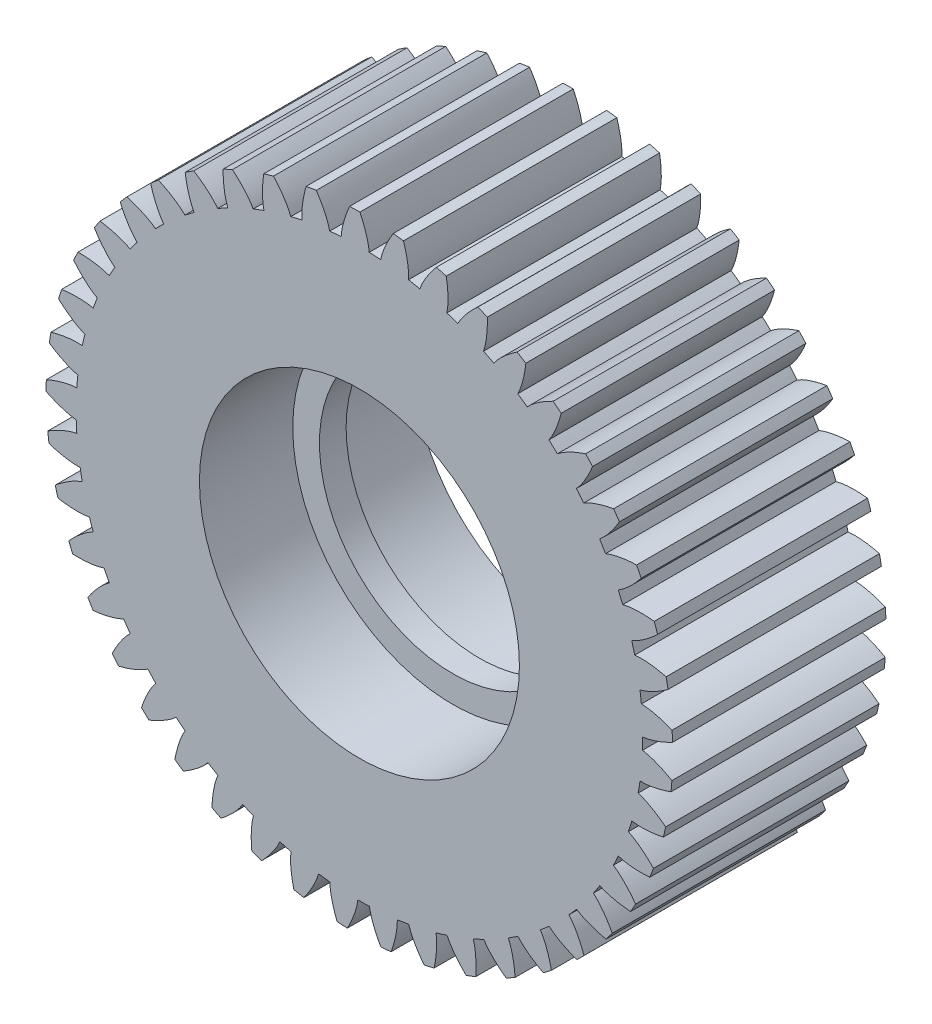
SolidWorks part; units mm, degrees
material "ABS"
ref_plane "Front Plane" through (0, 0, 0) normal (0, 0, 1) x (1, 0, 0)
ref_plane "Top Plane" through (0, 0, 0) normal (0, 1, 0) x (1, 0, 0)
ref_plane "Right Plane" through (0, 0, 0) normal (1, 0, 0) x (0, 0, -1)
sketch "Sketch1" plane through (0, 0, 0) normal (0, 0, 1) x (1, 0, 0)
  circle A0 centre (0, 0) radius 11.75
  dimension "D1" = 23.5
extrude "Boss-Extrude1" add sketch "Sketch1" along normal mid plane 8
sketch "Sketch2" plane through (0, 0, 0) normal (0, 0, 1) x (1, 0, 0)
  line L0 (0, 0) -> (10.5715, 0) construction
  line L1 (0, 0) -> (11.2477, -0.225) construction
  line L2 (0, 0) -> (10.5631, -0.4228) construction
  line L3 (10.5715, 0) -> (10.625, 0)
  line L4 (10.5631, -0.4228) -> (10.6165, -0.4249)
  circle A0 centre (0, 0) radius 11.25 construction
  circle A1 centre (0, 0) radius 10.5715 construction
  circle A2 centre (0, 0) radius 10.625
  circle A3 centre (0, 0) radius 11.75 construction
  circle A4 centre (0, 0) radius 11.75
  spline S0 degree 4 poles (10.5715, 0) (10.5752, 0.0001) (10.5853, 0.0004) (10.6044, 0.0016) (10.6356, 0.0045) (10.6753, 0.0095) (10.7265, 0.0174) (10.7865, 0.0288) (10.8523, 0.0433) (10.9236, 0.0613) (10.9945, 0.0812) (11.0648, 0.1028) (11.1346, 0.126) (11.2188, 0.1559) (11.3192, 0.1944) (11.4357, 0.2433) (11.5668, 0.3032) (11.6991, 0.369) (11.8282, 0.4376) (11.9573, 0.5114) (12.0813, 0.5859) (12.2085, 0.6678) (12.3252, 0.7457) (12.4542, 0.8378) (12.5578, 0.9136) (12.6924, 1.0187) (12.7713, 1.0823) (12.8629, 1.1585) (12.9032, 1.1933) (12.9281, 1.2147) knots 0 0 0 0 0 0.005377 0.015084 0.028532 0.04661 0.064855 0.092111 0.119476 0.146842 0.174209 0.201575 0.228941 0.256307 0.307035 0.361767 0.4165 0.471232 0.525964 0.580697 0.635429 0.690161 0.744894 0.799626 0.854358 0.909091 0.954545 1 1 1 1 1 construction
  spline S1 degree 4 poles (10.5715, 0) (10.5752, 0.0001) (10.5853, 0.0004) (10.6044, 0.0016) (10.6356, 0.0045) (10.6753, 0.0095) (10.7265, 0.0174) (10.7865, 0.0288) (10.8523, 0.0433) (10.9236, 0.0613) (10.9945, 0.0812) (11.0648, 0.1028) (11.1346, 0.126) (11.2188, 0.1559) (11.3192, 0.1944) (11.4357, 0.2433) (11.5668, 0.3032) (11.6991, 0.369) (11.8282, 0.4376) (11.9573, 0.5114) (12.0813, 0.5859) (12.2085, 0.6678) (12.3252, 0.7457) (12.4542, 0.8378) (12.5578, 0.9136) (12.6632, 0.9959) (12.7143, 1.0366) (12.7403, 1.0576) knots 0 0 0 0 0 0.005377 0.015084 0.028532 0.04661 0.064855 0.092111 0.119476 0.146842 0.174209 0.201575 0.228941 0.256307 0.307035 0.361767 0.4165 0.471232 0.525964 0.580697 0.635429 0.690161 0.744894 0.799626 0.854358 0.909091 0.909091 0.909091 0.909091 0.909091
  spline S2 degree 4 poles (10.5631, -0.4228) (10.5667, -0.423) (10.5768, -0.4237) (10.5959, -0.4257) (10.6269, -0.4298) (10.6664, -0.4364) (10.7172, -0.4464) (10.7768, -0.4602) (10.8419, -0.4773) (10.9124, -0.4981) (10.9824, -0.5208) (11.0518, -0.5452) (11.1207, -0.5712) (11.2036, -0.6045) (11.3024, -0.647) (11.4168, -0.7005) (11.5454, -0.7655) (11.675, -0.8366) (11.8012, -0.9103) (11.9273, -0.9892) (12.0482, -1.0686) (12.1721, -1.1555) (12.2856, -1.238) (12.4108, -1.3352) (12.5112, -1.4151) (12.6415, -1.5255) (12.7178, -1.5922) (12.8063, -1.672) (12.8452, -1.7084) (12.8691, -1.7308) knots 0 0 0 0 0 0.005377 0.015084 0.028532 0.04661 0.064855 0.092111 0.119476 0.146842 0.174209 0.201575 0.228941 0.256307 0.307035 0.361767 0.4165 0.471232 0.525964 0.580697 0.635429 0.690161 0.744894 0.799626 0.854358 0.909091 0.954545 1 1 1 1 1 construction
  spline S3 degree 4 poles (10.5631, -0.4228) (10.5667, -0.423) (10.5768, -0.4237) (10.5959, -0.4257) (10.6269, -0.4298) (10.6664, -0.4364) (10.7172, -0.4464) (10.7768, -0.4602) (10.8419, -0.4773) (10.9124, -0.4981) (10.9824, -0.5208) (11.0518, -0.5452) (11.1207, -0.5712) (11.2036, -0.6045) (11.3024, -0.647) (11.4168, -0.7005) (11.5454, -0.7655) (11.675, -0.8366) (11.8012, -0.9103) (11.9273, -0.9892) (12.0482, -1.0686) (12.1721, -1.1555) (12.2856, -1.238) (12.4108, -1.3352) (12.5112, -1.4151) (12.6133, -1.5016) (12.6627, -1.5442) (12.6878, -1.5663) knots 0 0 0 0 0 0.005377 0.015084 0.028532 0.04661 0.064855 0.092111 0.119476 0.146842 0.174209 0.201575 0.228941 0.256307 0.307035 0.361767 0.4165 0.471232 0.525964 0.580697 0.635429 0.690161 0.744894 0.799626 0.854358 0.909091 0.909091 0.909091 0.909091 0.909091
  dimension "D1" = 22.5
  dimension "D2" = 21.1431
  dimension "D3" = 21.25
  dimension "D4" = 1.146
  dimension "D5" = 1.146
extrude "Cut-Extrude1" cut sketch "Sketch2" against normal through all both and the other way through all contours A2 S3 A4 S1 region at (11.2841, -0.2257, 0)
pattern_circular "CirPattern2" count 45 over 360 about axis through (0, 0, 4) along (0, 0, -1) of "Cut-Extrude1"
sketch "Sketch3" plane through (0, 0, 4) normal (0, 0, 1) x (1, 0, 0)
  circle A0 centre (0, 0) radius 6
  dimension "D1" = 12
extrude "Cut-Extrude2" cut sketch "Sketch3" against normal blind 3.5
sketch "Sketch4" plane through (0, 0, 0.5) normal (0, 0, 1) x (1, 0, 0)
  circle A0 centre (0, 0) radius 5
  dimension "D1" = 10
extrude "Cut-Extrude3" cut sketch "Sketch4" against normal through all
mirror "Mirror1" about plane through (0, 0, 0) normal (0, 0, 1) of "Cut-Extrude2"
equation "\"Np\" = 45"
equation "\"module\" = 0.5"
equation "\"pressure angle\" = 20.0"
equation "\"h_a\" = 0.5"
equation "\"h_b\" = 0.625"
equation "\"clr_tip_root\" = 0.125"
equation "\"dp_p\" = 22.5"
equation "\"db_p\" = 21.14308396768294"
equation "\"D1@Sketch1\"= \"dp_p\" + 2*\"h_a\" "
equation "\"fw_p\" = 8.0"
equation "\"D1@Boss-Extrude1\"=\"fw_p\""
equation "\"D1@Sketch2\"=\"dp_p\""
equation "\"D2@Sketch2\"= \"db_p\""
equation "\"D3@Sketch2\"=\"dp_p\"- 2*\"h_b\""
equation "\"alpha_p\" = 0.8539582918412307"
equation "\"D4@Sketch2\"= 360 / ( 4 * \"Np\" ) - \"alpha_p\""
equation "\"beta_p\" = 2.2920834163175385"
equation "\"D5@Sketch2\"= 360 / ( 4 * \"Np\" ) - \"alpha_p\""
equation "\"D1@CirPattern2\"=\"Np\""
equation "\"Nr\" = 123"
equation "\"pressure_angle\" = 20.0"
equation "\"h_f\" = 0.625"
equation "\"dp_r\" = 61.5"
equation "\"db_r\" = 57.79109617833337"
equation "\"fw_r\" = 8.0"
equation "\"alpha_r\" = 0.8539582918412414"
equation "\"beta_r\" = 3.171331217828824"
equation "\"bearing_ID\" = 50"
equation "\"bearing_OD\" = 65"
equation "\"bearing_height\" = 7"
equation "\"clearance_planet\" = 1.5"
equation "\"case_dist\" = 6.5"
equation "\"Motor_case_OD_max\" = 96.5"
equation "\"case_mounting_PCD\" = 89.0"
equation "\"bearing mount thickness\" = 8"
equation "\"case_mounting_hole_dia\" = 3"
equation "\"output_mounting_PCD\" = 73"
equation "\"output_mounting_hole_dia\" = 4"
equation "\"clearance_case_mount_holes_shell_thickness\" = 1"
equation "\"motor_case_OD_base\" = 87.0"
equation "\"sec_carrier_thickness\" = 5"
equation "\"sun_coupler_hub_thickness\" = 4"
equation "\"clearance_sun_coupler_sec_carrier\" = 1.5"
equation "\"clearance_motor_and_case\" = 5"
equation "\"motor_OD\" = 72"
equation "\"Motor_case_thickness\" = 2.5"
equation "\"Motor_case_ID\" = 82"
equation "\"case_mounting_hole_shift\" = 1.0"
equation "\"output_mounting_nut_wrench_size\" = 7"
equation "\"output_mounting_nut_thickness\" = 3.2"
equation "\"case_mounting_hole_allen_socket_dia\" = 5.5"
equation "\"output_mounting_nut_depth\" = 3"
equation "\"case_mounting_bolt_depth\" = 4.5"
equation "\"Ns\" = 33"
equation "\"ring_radial_thickness\" = 5"
equation "\"ring_OD\" = 71.5"
equation "\"ring_to_chamfer_clearance\" = 2"
equation "\"Motor_case_OD_base_to_chamfer\" = 5"
equation "\"pattern_offset_from_motor_case_OD_base\" = 3"
equation "\"pattern_bulge_dia\" = 3"
equation "\"pattern_num_bulge\" = 18"
equation "\"pattern_depth\" = 2"
equation "\"motor_height\" = 27"
equation "\"case_mounting_wrench_size\" = 5.5"
equation "\"case_mounting_nut_clearance\" = 2"
equation "\"base_plate_thickness\" = 4"
equation "\"case_mounting_nut_thickness\" = 2.4"
equation "\"case_mounting_surface_height\" = 4"
equation "\"motor_mount_hole_PCD\" = 32"
equation "\"motor_mount_hole_dia\" = 4"
equation "\"motor_mount_hole_num\" = 4"
equation "\"central_hole_offset_from_motor_mount_PCD\" = 5"
equation "\"wire_slot_dist_from_center\" = 30"
equation "\"wire_slot_length\" = 10"
equation "\"wire_slot_radius\" = 2.5"
equation "\"driver_upper_holes_dist_from_center\" = 23"
equation "\"driver_lower_holes_dist_from_center\" = 15"
equation "\"driver_side_holes_dist_from_center\" = 20"
equation "\"driver_mount_holes_dia\" = 2.5"
equation "\"driver_mount_inserts_OD\" = 3.5"
equation "\"driver_mount_thickness\" = 1.5"
equation "\"driver_mount_height\" = 4"
equation "\"air_flow_hole_offset\" = 3"
equation "\"num_planet\" = 3"
equation "\"planet_pin_bolt_dia\" = 5"
equation "\"planet_pin_socket_head_dia\" = 8.5"
equation "\"carrier_PCD\" = 39.0"
equation "\"planet_shaft_dia\" = 8"
equation "\"planet_shaft_step_offset\" = 1"
equation "\"carrier_trapezoidal_support_sun_offset\" = 5"
equation "\"carrier_trapezoidal_support_hole_PCD_offset_bearing_ID\" = 4"
equation "\"carrier_trapezoidal_support_hole_dia\" = 3"
equation "\"carrier_trapezoidal_support_hole_socket_head_dia\" = 5.5"
equation "\"carrier_bearing_step_width\" = 1.5"
equation "\"standard_clearance_1_5mm\" = 1.5"
equation "\"standard_fillet_1_5mm\" = 1.5"
equation "\"sun_shaft_bearing_OD\" = 16"
equation "\"sun_shaft_bearing_width\" = 5"
equation "\"standard_bearing_insertion_chamfer\" = 0.5"
equation "\"carrier_trapezoidal_support_hole_wrench_size\" = 5.5"
equation "\"planet_pin_bolt_wrench_size\" = 8"
equation "\"planet_bearing_OD\" = 12"
equation "\"planet_bearing_width\" = 3.5"
equation "\"planet_bore\" = 10"
equation "\"D1@Cut-Extrude2\"=\"planet_bearing_width\""
equation "\"D1@Sketch3\"=\"planet_bearing_OD\""
equation "\"D1@Sketch4\"=\"planet_bore\""
equation "\"motor_output_hole_PCD\" = 22"
equation "\"motor_output_hole_dia\" = 3"
equation "\"motor_output_hole_num\" = 4"
equation "\"dp_s\" = 16.5"
equation "\"db_s\" = 15.50492824296749"
equation "\"fw_s_calc\" = 1.2595130854287364"
equation "\"alpha_s\" = 0.8539582918412449"
equation "\"beta_s\" = 3.7466288708629643"
equation "\"sun_shaft_bearing_ID\" = 8"
equation "\"sun_hub_dia\" = 31.0"
equation "\"sun_central_bolt_dia\" = 5"
equation "\"sun_central_bolt_socket_head_dia\" = 8.5"
equation "\"fw_s_used\" = 16.0"
equation "\"motor_output_hole_CSK_OD\" = 6"
equation "\"motor_output_hole_CSK_head_height\" = 1.5"
equation "\"bearing_retainer_thickness\" = 2"
